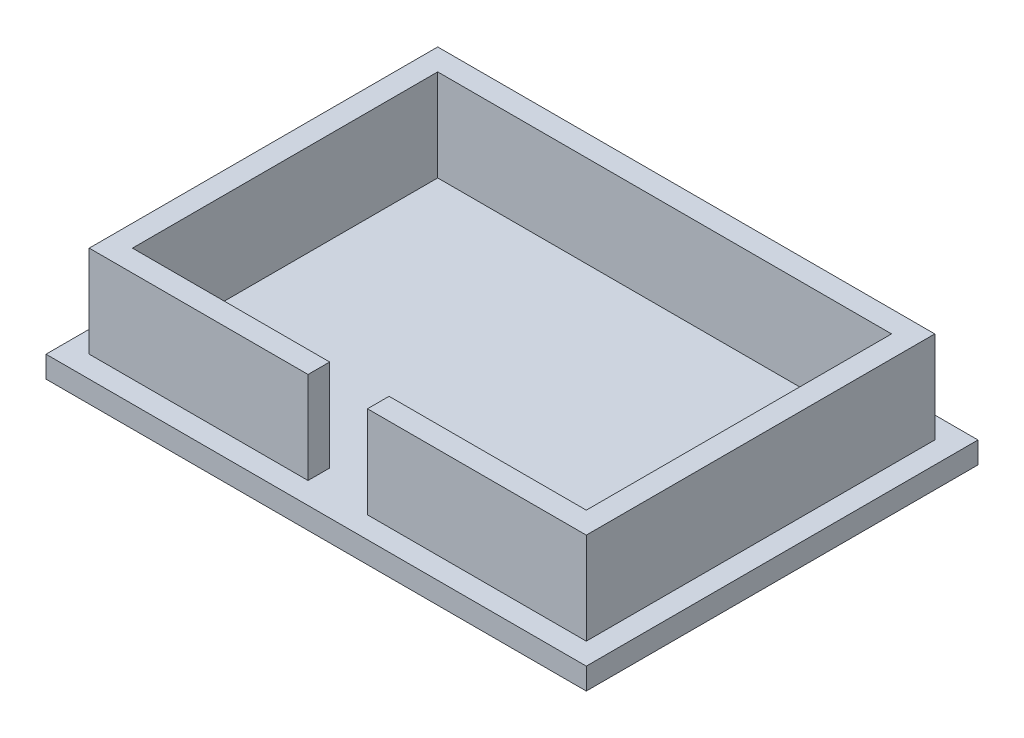
SolidWorks part; units mm, degrees
ref_plane "Front Plane" through (0, 0, 0) normal (0, 0, 1) x (1, 0, 0)
ref_plane "Top Plane" through (0, 0, 0) normal (0, 1, 0) x (1, 0, 0)
ref_plane "Right Plane" through (0, 0, 0) normal (1, 0, 0) x (0, 0, -1)
sketch "Sketch2" plane through (0, 0, 0) normal (0, 1, 0) x (1, 0, 0)
  line L0 (-42.9708, 29.2873) -> (-38.9708, 29.2873)
  line L1 (-38.9708, 29.2873) -> (45.0292, 29.2873)
  line L2 (-38.9708, 29.2873) -> (-38.9708, -27.2127)
  line L3 (-38.9708, -27.2127) -> (45.0292, -27.2127)
  line L4 (45.0292, 29.2873) -> (45.0292, -27.2127)
  line L5 (-42.9708, 33.2873) -> (49.0292, 33.2873)
  line L6 (-42.9708, 33.2873) -> (-42.9708, -31.2127)
  line L7 (-42.9708, -31.2127) -> (49.0292, -31.2127)
  line L8 (49.0292, 33.2873) -> (49.0292, -31.2127)
  line L9 (-38.9708, 33.2873) -> (-38.9708, 29.2873)
  line L10 (49.0292, -27.2127) -> (45.0292, -27.2127)
  line L11 (45.0292, -31.2127) -> (45.0292, -27.2127)
  line L12 (-42.9708, 37.2873) -> (-42.9708, 33.2873)
  line L13 (-46.9708, 37.2873) -> (53.0292, 37.2873)
  line L14 (-46.9708, 37.2873) -> (-46.9708, -35.2127)
  line L15 (-46.9708, -35.2127) -> (53.0292, -35.2127)
  line L16 (53.0292, 37.2873) -> (53.0292, -35.2127)
  line L17 (-46.9708, 33.2873) -> (-42.9708, 33.2873)
  line L18 (53.0292, -31.2127) -> (49.0292, -31.2127)
  line L19 (49.0292, -35.2127) -> (49.0292, -31.2127)
  dimension "D1" = 56.5
  dimension "D2" = 84
  dimension "D3" = 4
  dimension "D4" = 4
  dimension "D5" = 4
  dimension "D6" = 4
  dimension "D7" = 4
  dimension "D8" = 4
  dimension "D9" = 4
  dimension "D10" = 4
extrude "Boss-Extrude1" add sketch "Sketch2" along normal blind 4 contours L18 L16 L13 L12 L5 L8 | L19 L15 L16 L18 | L15 L19 L7 L6 L17 L14 | L4 L1 L2 L3 | L14 L17 L12 L13 | L9 L5 L6 L0 | L10 L8 L5 L9 L1 L4 | L7 L11 L3 L2 L0 L6 | L11 L7 L8 L10 region at (-40.9708, 0, -31.2873) region at (-44.1502, 0, 0.9627) region at (-40.9708, 0, -28.2194) region at (-37.9029, 0, -31.2873) region at (3.0292, 0, -1.0373) region at (-41.7915, 0, -35.2873) region at (-44.9708, 0, -35.2873) region at (47.0292, 0, 29.2127) region at (51.0292, 0, 33.2127)
extrude "Boss-Extrude2" add sketch "Sketch2<3>" along normal blind 21 contours L10 L8 L5 L9 L1 L4 | L9 L5 L6 L0 | L7 L11 L3 L2 L0 L6 | L11 L7 L8 L10 region at (-40.9708, 0, -31.2873) region at (-40.9708, 0, -28.2194) region at (-37.9029, 0, -31.2873) region at (47.0292, 0, 29.2127)
sketch "Sketch2<3>" plane through (0, 0, 0) normal (0, 1, 0) x (1, 0, 0) same geometry as "Sketch2"
sketch "Sketch3" plane through (0, 0, 31.2127) normal (0, 0, 1) x (1, 0, 0)
  line L0 (-42.9708, 21) -> (49.0292, 4)
  line L1 (3.0292, 12.5) -> (3.0292, 21)
  line L2 (-42.9708, 21) -> (49.0292, 21) construction
  line L3 (3.0292, 21) -> (-2.4708, 21)
  line L4 (-2.4708, 21) -> (-2.4708, 4)
  line L5 (49.0292, 4) -> (-42.9708, 4) construction
  line L6 (-2.4708, 4) -> (8.5292, 4)
  line L7 (8.5292, 4) -> (8.5292, 21)
  line L8 (8.5292, 21) -> (3.0292, 21)
  line M6 (-42.9708, 4) -> (49.0292, 4)
  line M8 (49.0292, 21) -> (-42.9708, 21)
  dimension "D1" = 5.5
extrude "Cut-Extrude1" cut sketch "Sketch3" against normal blind 10 contours L0 L7 L1 M8 | L4 L0 L1 M8 | L7 L0 L4 M6 region at (0.3374, 16.9987, 31.2127) region at (2.81, 8.2703, 31.2127) region at (5.8309, 16.4911, 31.2127)
